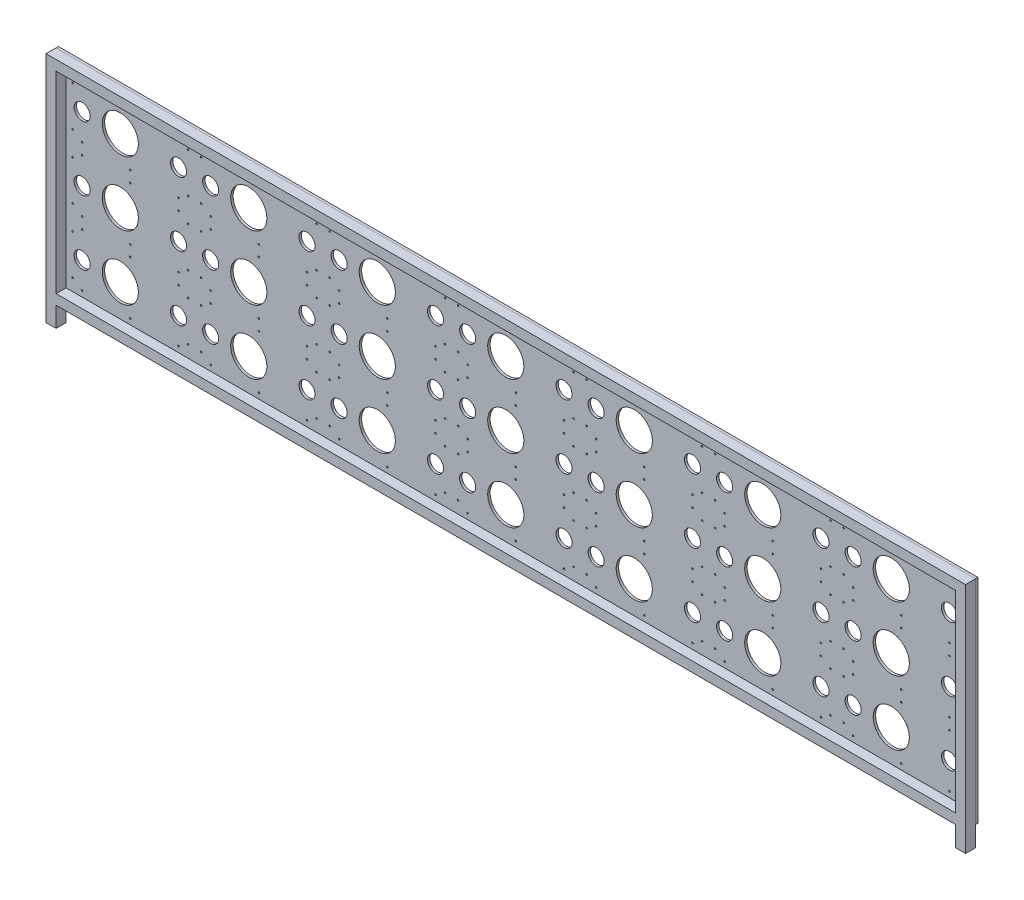
SolidWorks part; units mm, degrees
material "1060 Alloy"
ref_plane "Front Plane" through (0, 0, 0) normal (0, 0, 1) x (1, 0, 0)
ref_plane "Top Plane" through (0, 0, 0) normal (0, 1, 0) x (1, 0, 0)
ref_plane "Right Plane" through (0, 0, 0) normal (1, 0, 0) x (0, 0, -1)
sketch "Sketch8" plane through (0, 0, 0) normal (0, 0, 1) x (1, 0, 0)
  line L0 (0, 265) -> (0, 0) construction
  line L1 (-1145, 265) -> (1145, 265)
  line L2 (-1145, 265) -> (-1145, -265)
  line L3 (-1145, -265) -> (1145, -265)
  line L4 (1145, 265) -> (1145, -265)
  line L5 (0, 0) -> (0, -265) construction
  dimension "D1" = 530
  dimension "D2" = 2290
extrude "Boss-Extrude7" add sketch "Sketch8" against normal blind 6
sketch "Sketch5" plane through (0, 0, 0) normal (0, 0, 1) x (1, 0, 0)
  line L0 (-1145, 265) -> (1145, 265)
  line L1 (-1120, 240) -> (1120, 240)
  line L2 (-1120, 240) -> (-1120, -240)
  line L3 (-1120, -240) -> (1120, -240)
  line L4 (1120, 240) -> (1120, -240)
  line L5 (1145, 265) -> (1145, -315)
  line L6 (1145, -315) -> (1120, -315)
  line L7 (1120, -315) -> (1120, -265)
  line L8 (-1145, -265) -> (1145, -265) construction
  line L9 (1120, -265) -> (-1120, -265)
  line L10 (-1120, -265) -> (-1120, -315)
  line L11 (-1120, -315) -> (-1145, -315)
  line L12 (-1145, -315) -> (-1145, 265)
  dimension "D1" = 25
  dimension "D2" = 25
  dimension "D3" = 25
  dimension "D4" = 25
  dimension "D5" = 580
extrude "Boss-Extrude8" add sketch "Sketch5" along normal blind 25 separate body
sketch "Sketch4" plane through (0, 0, 0) normal (0, 0, 1) x (1, 0, 0)
  line L0 (-1103.75, 210) -> (-816.25, 210) construction
  line L1 (-1103.75, 110) -> (-816.25, 110) construction
  line L2 (-816.25, 210) -> (-816.25, 110) construction
  line L3 (-960, 93.75) -> (-960, 160) construction
  line L4 (-960, 160) -> (-960, 226.25) construction
  line L5 (-1103.75, 110) -> (-1103.75, 210) construction
  line L6 (-1103.75, 160) -> (-960, 160) construction
  line L7 (-960, 160) -> (-816.25, 160) construction
  line L8 (-960, 240) -> (-960, 226.25) construction
  line L9 (-1120, 240) -> (-800, 240) construction
  line L10 (-1120, 240) -> (-1120, 80) construction
  line L11 (-1120, 80) -> (-800, 80) construction
  line L12 (-800, 240) -> (-800, 80) construction
  line L13 (-960, 93.75) -> (-960, 80) construction
  line L14 (-1103.75, 160) -> (-1120, 160) construction
  line L15 (-816.25, 160) -> (-800, 160) construction
  line L16 (-800, 80) -> (-800, 0) construction
  line L17 (-960, 226) -> (-960, 160) construction
  line L18 (-1080, 94) -> (-840, 94) construction
  line L19 (-1080, 94) -> (-1080, 226) construction
  line L20 (-1080, 226) -> (-840, 226) construction
  line L21 (-840, 94) -> (-840, 226) construction
  line L22 (-960, 160) -> (-960, 94) construction
  line L23 (-840, 160) -> (-520, 160) construction
  line L24 (-1080, 160) -> (-1080, 0) construction
  line L25 (-800, 0) -> (0, 0) construction
  circle A0 centre (-1103.75, 210) radius 2
  circle A1 centre (-1103.75, 110) radius 2
  circle A2 centre (-960, 226.25) radius 2
  circle A3 centre (-816.25, 210) radius 2
  circle A4 centre (-960, 93.75) radius 2
  circle A5 centre (-816.25, 110) radius 2
  circle A6 centre (-1080, 94) radius 2
  circle A7 centre (-1080, 226) radius 2
  circle A8 centre (-840, 226) radius 2
  circle A9 centre (-840, 94) radius 2
  circle A10 centre (-760, 94) radius 2
  circle A11 centre (-783.75, 110) radius 2
  circle A12 centre (-760, 160) radius 20
  circle A13 centre (-783.75, 210) radius 2
  circle A14 centre (-760, 226) radius 2
  circle A15 centre (-665, 160) radius 45
  circle A16 centre (-640, 226.25) radius 2
  circle A17 centre (-640, 93.75) radius 2
  circle A18 centre (-520, 94) radius 2
  circle A19 centre (-496.25, 110) radius 2
  circle A20 centre (-520, 160) radius 20
  circle A21 centre (-520, 226) radius 2
  circle A22 centre (-496.25, 210) radius 2
  circle A23 centre (-760, -66) radius 2
  circle A24 centre (-783.75, -50) radius 2
  circle A25 centre (-760, 0) radius 20
  circle A26 centre (-783.75, 50) radius 2
  circle A27 centre (-760, 66) radius 2
  circle A28 centre (-665, 0) radius 45
  circle A29 centre (-640, 66.25) radius 2
  circle A30 centre (-640, -66.25) radius 2
  circle A31 centre (-520, -66) radius 2
  circle A32 centre (-496.25, -50) radius 2
  circle A33 centre (-520, 0) radius 20
  circle A34 centre (-520, 66) radius 2
  circle A35 centre (-496.25, 50) radius 2
  circle A36 centre (-1080, -226) radius 2
  circle A37 centre (-1103.75, -210) radius 2
  circle A38 centre (-1080, -160) radius 20
  circle A39 centre (-1103.75, -110) radius 2
  circle A40 centre (-1080, -94) radius 2
  circle A41 centre (-985, -160) radius 45
  circle A42 centre (-960, -93.75) radius 2
  circle A43 centre (-960, -226.25) radius 2
  circle A44 centre (-840, -226) radius 2
  circle A45 centre (-816.25, -210) radius 2
  circle A46 centre (-840, -160) radius 20
  circle A47 centre (-840, -94) radius 2
  circle A48 centre (-1080, 160) radius 20
  circle A49 centre (-985, 160) radius 45
  circle A50 centre (-840, 160) radius 20
  circle A51 centre (-816.25, -110) radius 2
  circle A52 centre (-760, -226) radius 2
  circle A53 centre (-783.75, -210) radius 2
  circle A54 centre (-760, -160) radius 20
  circle A55 centre (-783.75, -110) radius 2
  circle A56 centre (-760, -94) radius 2
  circle A57 centre (-665, -160) radius 45
  circle A58 centre (-640, -93.75) radius 2
  circle A59 centre (-640, -226.25) radius 2
  circle A60 centre (-520, -226) radius 2
  circle A61 centre (-496.25, -210) radius 2
  circle A62 centre (-520, -160) radius 20
  circle A63 centre (-520, -94) radius 2
  circle A64 centre (-496.25, -110) radius 2
  circle A65 centre (-1080, -66) radius 2
  circle A66 centre (-1103.75, -50) radius 2
  circle A67 centre (-1080, 0) radius 20
  circle A68 centre (-1103.75, 50) radius 2
  circle A69 centre (-1080, 66) radius 2
  circle A70 centre (-985, 0) radius 45
  circle A71 centre (-960, 66.25) radius 2
  circle A72 centre (-960, -66.25) radius 2
  circle A73 centre (-840, -66) radius 2
  circle A74 centre (-816.25, -50) radius 2
  circle A75 centre (-840, 0) radius 20
  circle A76 centre (-840, 66) radius 2
  circle A77 centre (-816.25, 50) radius 2
  circle A78 centre (-440, -226) radius 2
  circle A79 centre (-463.75, -210) radius 2
  circle A80 centre (-440, -160) radius 20
  circle A81 centre (-463.75, -110) radius 2
  circle A82 centre (-440, -94) radius 2
  circle A83 centre (-345, -160) radius 45
  circle A84 centre (-320, -93.75) radius 2
  circle A85 centre (-320, -226.25) radius 2
  circle A86 centre (-200, -226) radius 2
  circle A87 centre (-176.25, -210) radius 2
  circle A88 centre (-200, -160) radius 20
  circle A89 centre (-200, -94) radius 2
  circle A90 centre (-176.25, -110) radius 2
  circle A91 centre (-120, -226) radius 2
  circle A92 centre (-143.75, -210) radius 2
  circle A93 centre (-120, -160) radius 20
  circle A94 centre (-143.75, -110) radius 2
  circle A95 centre (-120, -94) radius 2
  circle A96 centre (-25, -160) radius 45
  circle A97 centre (0, -93.75) radius 2
  circle A98 centre (0, -226.25) radius 2
  circle A99 centre (120, -226) radius 2
  circle A100 centre (143.75, -210) radius 2
  circle A101 centre (120, -160) radius 20
  circle A102 centre (120, -94) radius 2
  circle A103 centre (143.75, -110) radius 2
  circle A104 centre (-440, 94) radius 2
  circle A105 centre (-463.75, 110) radius 2
  circle A106 centre (-440, 160) radius 20
  circle A107 centre (-463.75, 210) radius 2
  circle A108 centre (-440, 226) radius 2
  circle A109 centre (-345, 160) radius 45
  circle A110 centre (-320, 226.25) radius 2
  circle A111 centre (-320, 93.75) radius 2
  circle A112 centre (-200, 94) radius 2
  circle A113 centre (-176.25, 110) radius 2
  circle A114 centre (-200, 160) radius 20
  circle A115 centre (-200, 226) radius 2
  circle A116 centre (-176.25, 210) radius 2
  circle A117 centre (-120, 94) radius 2
  circle A118 centre (-143.75, 110) radius 2
  circle A119 centre (-120, 160) radius 20
  circle A120 centre (-143.75, 210) radius 2
  circle A121 centre (-120, 226) radius 2
  circle A122 centre (-25, 160) radius 45
  circle A123 centre (0, 226.25) radius 2
  circle A124 centre (0, 93.75) radius 2
  circle A125 centre (120, 94) radius 2
  circle A126 centre (143.75, 110) radius 2
  circle A127 centre (120, 160) radius 20
  circle A128 centre (120, 226) radius 2
  circle A129 centre (143.75, 210) radius 2
  circle A130 centre (200, 94) radius 2
  circle A131 centre (176.25, 110) radius 2
  circle A132 centre (200, 160) radius 20
  circle A133 centre (176.25, 210) radius 2
  circle A134 centre (200, 226) radius 2
  circle A135 centre (295, 160) radius 45
  circle A136 centre (320, 226.25) radius 2
  circle A137 centre (320, 93.75) radius 2
  circle A138 centre (440, 94) radius 2
  circle A139 centre (463.75, 110) radius 2
  circle A140 centre (440, 160) radius 20
  circle A141 centre (440, 226) radius 2
  circle A142 centre (463.75, 210) radius 2
  circle A143 centre (520, 94) radius 2
  circle A144 centre (496.25, 110) radius 2
  circle A145 centre (520, 160) radius 20
  circle A146 centre (496.25, 210) radius 2
  circle A147 centre (520, 226) radius 2
  circle A148 centre (615, 160) radius 45
  circle A149 centre (640, 226.25) radius 2
  circle A150 centre (640, 93.75) radius 2
  circle A151 centre (760, 94) radius 2
  circle A152 centre (783.75, 110) radius 2
  circle A153 centre (760, 160) radius 20
  circle A154 centre (760, 226) radius 2
  circle A155 centre (783.75, 210) radius 2
  circle A156 centre (840, 94) radius 2
  circle A157 centre (816.25, 110) radius 2
  circle A158 centre (840, 160) radius 20
  circle A159 centre (816.25, 210) radius 2
  circle A160 centre (840, 226) radius 2
  circle A161 centre (935, 160) radius 45
  circle A162 centre (960, 226.25) radius 2
  circle A163 centre (960, 93.75) radius 2
  circle A164 centre (1080, 94) radius 2
  circle A165 centre (1103.75, 110) radius 2
  circle A166 centre (1080, 160) radius 20
  circle A167 centre (1080, 226) radius 2
  circle A168 centre (1103.75, 210) radius 2
  circle A169 centre (-440, -66) radius 2
  circle A170 centre (-463.75, -50) radius 2
  circle A171 centre (-440, 0) radius 20
  circle A172 centre (-463.75, 50) radius 2
  circle A173 centre (-440, 66) radius 2
  circle A174 centre (-345, 0) radius 45
  circle A175 centre (-320, 66.25) radius 2
  circle A176 centre (-320, -66.25) radius 2
  circle A177 centre (-200, -66) radius 2
  circle A178 centre (-176.25, -50) radius 2
  circle A179 centre (-200, 0) radius 20
  circle A180 centre (-200, 66) radius 2
  circle A181 centre (-176.25, 50) radius 2
  circle A182 centre (-120, -66) radius 2
  circle A183 centre (-143.75, -50) radius 2
  circle A184 centre (-120, 0) radius 20
  circle A185 centre (-143.75, 50) radius 2
  circle A186 centre (-120, 66) radius 2
  circle A187 centre (-25, 0) radius 45
  circle A188 centre (0, 66.25) radius 2
  circle A189 centre (0, -66.25) radius 2
  circle A190 centre (120, -66) radius 2
  circle A191 centre (143.75, -50) radius 2
  circle A192 centre (120, 0) radius 20
  circle A193 centre (120, 66) radius 2
  circle A194 centre (143.75, 50) radius 2
  circle A195 centre (200, -66) radius 2
  circle A196 centre (176.25, -50) radius 2
  circle A197 centre (200, 0) radius 20
  circle A198 centre (176.25, 50) radius 2
  circle A199 centre (200, 66) radius 2
  circle A200 centre (295, 0) radius 45
  circle A201 centre (320, 66.25) radius 2
  circle A202 centre (320, -66.25) radius 2
  circle A203 centre (440, -66) radius 2
  circle A204 centre (463.75, -50) radius 2
  circle A205 centre (440, 0) radius 20
  circle A206 centre (440, 66) radius 2
  circle A207 centre (463.75, 50) radius 2
  circle A208 centre (520, -66) radius 2
  circle A209 centre (496.25, -50) radius 2
  circle A210 centre (520, 0) radius 20
  circle A211 centre (496.25, 50) radius 2
  circle A212 centre (520, 66) radius 2
  circle A213 centre (615, 0) radius 45
  circle A214 centre (640, 66.25) radius 2
  circle A215 centre (640, -66.25) radius 2
  circle A216 centre (760, -66) radius 2
  circle A217 centre (783.75, -50) radius 2
  circle A218 centre (760, 0) radius 20
  circle A219 centre (760, 66) radius 2
  circle A220 centre (783.75, 50) radius 2
  circle A221 centre (840, -66) radius 2
  circle A222 centre (816.25, -50) radius 2
  circle A223 centre (840, 0) radius 20
  circle A224 centre (816.25, 50) radius 2
  circle A225 centre (840, 66) radius 2
  circle A226 centre (935, 0) radius 45
  circle A227 centre (960, 66.25) radius 2
  circle A228 centre (960, -66.25) radius 2
  circle A229 centre (1080, -66) radius 2
  circle A230 centre (1103.75, -50) radius 2
  circle A231 centre (1080, 0) radius 20
  circle A232 centre (1080, 66) radius 2
  circle A233 centre (1103.75, 50) radius 2
  circle A234 centre (200, -226) radius 2
  circle A235 centre (176.25, -210) radius 2
  circle A236 centre (200, -160) radius 20
  circle A237 centre (176.25, -110) radius 2
  circle A238 centre (200, -94) radius 2
  circle A239 centre (295, -160) radius 45
  circle A240 centre (320, -93.75) radius 2
  circle A241 centre (320, -226.25) radius 2
  circle A242 centre (440, -226) radius 2
  circle A243 centre (463.75, -210) radius 2
  circle A244 centre (440, -160) radius 20
  circle A245 centre (440, -94) radius 2
  circle A246 centre (463.75, -110) radius 2
  circle A247 centre (520, -226) radius 2
  circle A248 centre (496.25, -210) radius 2
  circle A249 centre (520, -160) radius 20
  circle A250 centre (496.25, -110) radius 2
  circle A251 centre (520, -94) radius 2
  circle A252 centre (615, -160) radius 45
  circle A253 centre (640, -93.75) radius 2
  circle A254 centre (640, -226.25) radius 2
  circle A255 centre (760, -226) radius 2
  circle A256 centre (783.75, -210) radius 2
  circle A257 centre (760, -160) radius 20
  circle A258 centre (760, -94) radius 2
  circle A259 centre (783.75, -110) radius 2
  circle A260 centre (840, -226) radius 2
  circle A261 centre (816.25, -210) radius 2
  circle A262 centre (840, -160) radius 20
  circle A263 centre (816.25, -110) radius 2
  circle A264 centre (840, -94) radius 2
  circle A265 centre (935, -160) radius 45
  circle A266 centre (960, -93.75) radius 2
  circle A267 centre (960, -226.25) radius 2
  circle A268 centre (1080, -226) radius 2
  circle A269 centre (1103.75, -210) radius 2
  circle A270 centre (1080, -160) radius 20
  circle A271 centre (1080, -94) radius 2
  circle A272 centre (1103.75, -110) radius 2
  dimension "D1" = 4
  dimension "D14" = 40
  dimension "D15" = 90
  dimension "D17" = 40
  dimension "D6" = 4
  dimension "D2" = 16.25
  dimension "D3" = 160
  dimension "D4" = 320
  dimension "D5" = 30
  dimension "D9" = 80
  dimension "D10" = 7
  dimension "D11" = 132.5
  dimension "D12" = 287.5
  dimension "D13" = 40
  dimension "D16" = 40
  dimension "D18" = 135
  dimension "D7" = 40
  dimension "D8" = 14
  dimension "D20" = 320
  dimension "D21" = 160
  dimension "D22" = 800
  dimension "D19" = 3
extrude "Cut-Extrude1" cut sketch "Sketch4" against normal through all
